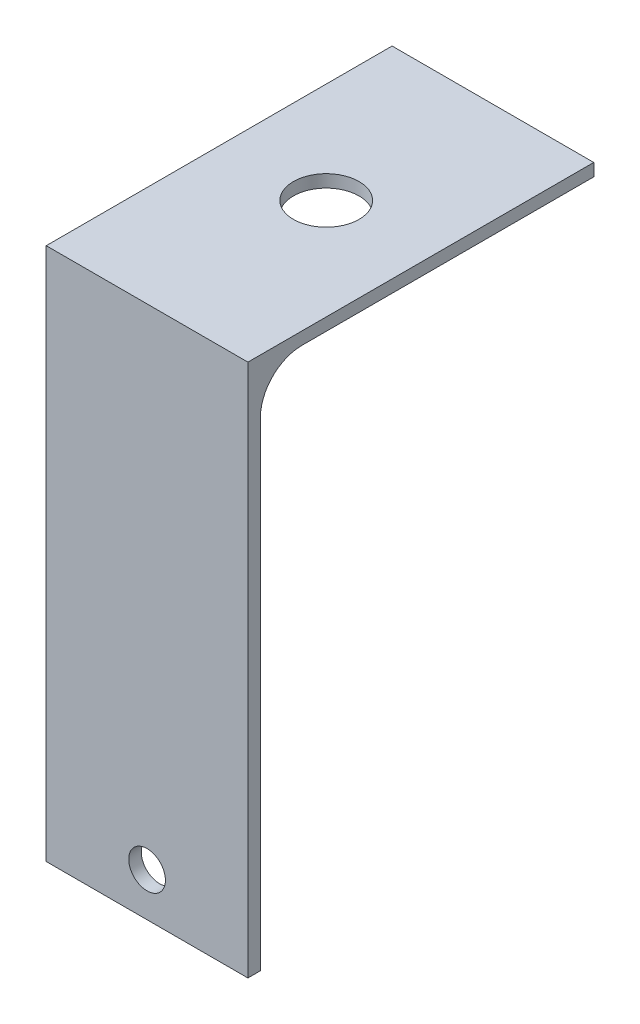
SolidWorks part; units mm, degrees
material "1060 Alloy"
ref_plane "Front Plane" through (0, 0, 0) normal (0, 0, 1) x (1, 0, 0)
ref_plane "Top Plane" through (0, 0, 0) normal (0, 1, 0) x (1, 0, 0)
ref_plane "Right Plane" through (0, 0, 0) normal (1, 0, 0) x (0, 0, -1)
sketch "Sketch1" plane through (0, 0, 0) normal (0, 0, 1) x (1, 0, 0)
  line L1 (12.1, -32) -> (-12.1, -32)
  line L2 (12.1, -32) -> (12.1, 32)
  line L3 (12.1, 32) -> (-12.1, 32)
  line L4 (-12.1, -32) -> (-12.1, 32)
  line L5 (12.1, -32) -> (-12.1, 32) construction
  line L6 (12.1, 32) -> (-12.1, -32) construction
  point P0 (0, 0)
  dimension "Base" = 24.2
  dimension "ServoToTop" = 64
extrude "Boss-Extrude1" add sketch "Sketch1" along normal blind 1.5
sketch "Sketch2" plane through (0, 0, 1.5) normal (0, 0, 1) x (1, 0, 0)
  line L0 (-12.1, -32) -> (12.1, -32) construction
  line L1 (12.1, -32) -> (12.1, 32) construction
  circle A0 centre (0, -26.8) radius 2.2
  dimension "D2" = 4.4
  dimension "D1" = 5.2
  dimension "D3" = 12.1
extrude "Cut-Extrude1" cut sketch "Sketch2" against normal through all
sketch "Sketch4" plane through (0, 32, 0) normal (0, 1, 0) x (1, 0, 0)
  line L0 (-12.1, -1.5) -> (-12.1, 0) construction
  line L1 (-12.1, 0) -> (12.1, 0)
  line L2 (-12.1, 0) -> (-12.1, 40)
  line L3 (-12.1, 40) -> (12.1, 40)
  line L4 (12.1, 0) -> (12.1, 40)
  line L5 (12.1, -1.5) -> (12.1, 0) construction
  dimension "BaseTopLength" = 40
extrude "Boss-Extrude2" add sketch "Sketch4" against normal blind 1.5
sketch "Sketch5" plane through (0, 30.5, 0) normal (0, -1, 0) x (1, 0, 0)
  line L0 (-12.1, 0) -> (12.1, 0) construction
  line L1 (-12.1, -40) -> (-12.1, 0) construction
  circle A0 centre (0, -20) radius 3.937
  dimension "D1" = 7.874
  dimension "D2" = 20
  dimension "D3" = 12.1
extrude "Cut-Extrude2" cut sketch "Sketch5" against normal through all
fillet "Fillet1" radius 5 1 edges at (0, 30.5, 0) type face fillet first side face at (0, 30.5, -23.937) second side face at (2.2, -26.8, 0)
